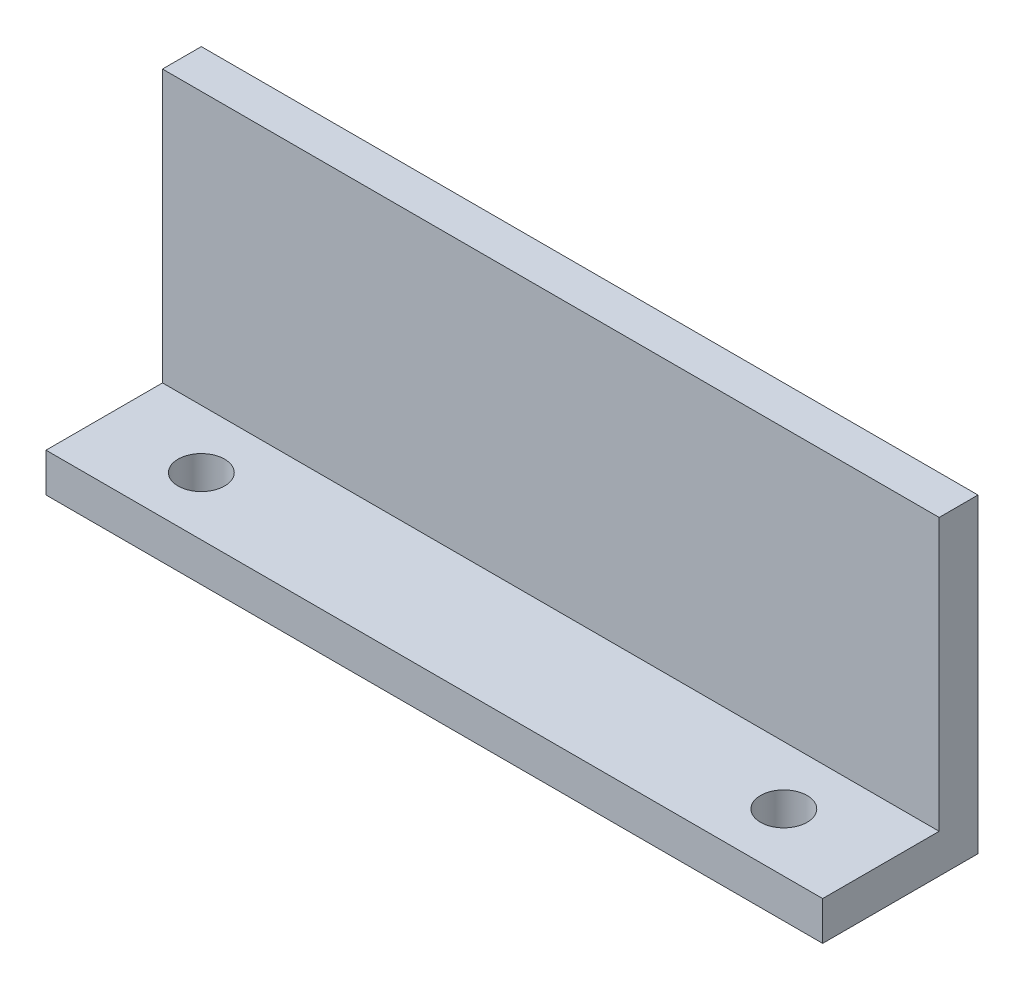
SolidWorks part; units mm, degrees
ref_plane "Płaszczyzna przednia" through (0, 0, 0) normal (0, 0, 1) x (1, 0, 0)
ref_plane "Płaszczyzna górna" through (0, 0, 0) normal (0, 1, 0) x (1, 0, 0)
ref_plane "Płaszczyzna prawa" through (0, 0, 0) normal (1, 0, 0) x (0, 0, -1)
sketch "Szkic1" plane through (0, 0, 0) normal (0, 0, 1) x (1, 0, 0)
  line L1 (-100, -40) -> (100, -40)
  line L2 (-100, -40) -> (-100, 40)
  line L3 (-100, 40) -> (100, 40)
  line L4 (100, -40) -> (100, 40)
  line L5 (-100, -40) -> (100, 40) construction
  line L6 (-100, 40) -> (100, -40) construction
  point P0 (0, 0)
  dimension "D1" = 200
  dimension "D2" = 80
extrude "Dodanie-wyciągnięcie1" add sketch "Szkic1" along normal blind 10
sketch "Szkic2" plane through (0, 0, 10) normal (0, 0, 1) x (1, 0, 0)
  line L0 (100, -40) -> (100, 40) construction
  line L1 (-100, -40) -> (100, -40)
  line L2 (-100, -40) -> (-100, -30)
  line L3 (-100, -30) -> (100, -30)
  line L4 (100, -40) -> (100, -30)
  dimension "D1" = 10
extrude "Dodanie-wyciągnięcie2" add sketch "Szkic2" along normal blind 30
hole_wizard "Otwór pod śrubę M101" positions "Szkic3" profile "Szkic4" hole size "M10" standard "Ansi Metric" end condition through all
sketch "Szkic3" plane through (0, -30, 0) normal (0, 1, 0) x (1, 0, 0)
  line L0 (100, -40) -> (-100, -40) construction
  line L1 (-100, -40) -> (-100, -10) construction
  point P0 (-75, -25)
  dimension "D1" = 15
  dimension "D2" = 25
sketch "Szkic4" plane through (-75, -30, 25) normal (1, 0, 0) x (0, 0, 1)
  line L0 (0, 0) -> (0, 10)
  line L1 (0, 10) -> (6, 10)
  line L2 (6, 10) -> (6, 0)
  line L5 (6, 0) -> (0, 0)
  line L11 (0, -6.35) -> (0, 107.95) construction
  dimension "Średnica otworu na wylot" = 12
  dimension "Głębokość otworu na wylot" = 10
pattern_linear "Szyk liniowy2" count 2 spacing 150 along (1, 0, 0) of "Otwór pod śrubę M101"
